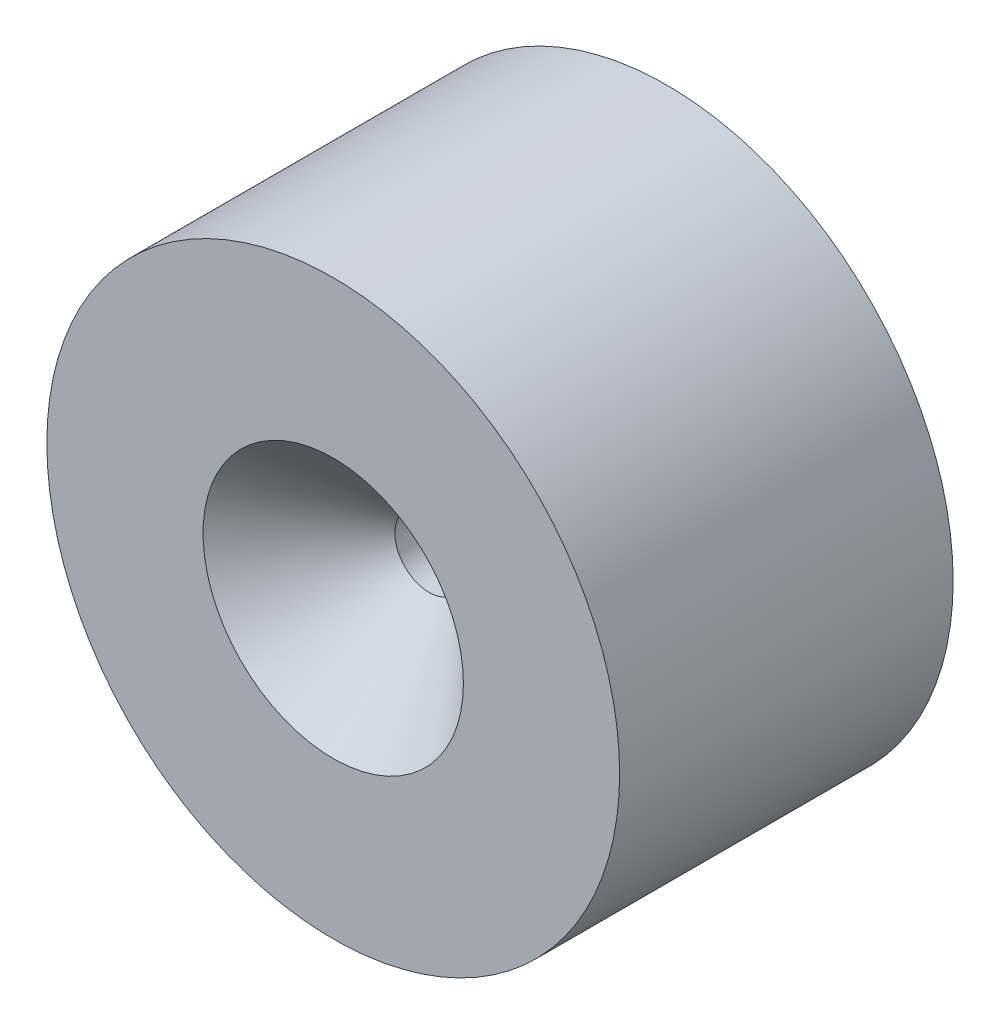
SolidWorks part; units mm, degrees
ref_plane "Front Plane" through (0, 0, 0) normal (0, 0, 1) x (1, 0, 0)
ref_plane "Top Plane" through (0, 0, 0) normal (0, 1, 0) x (1, 0, 0)
ref_plane "Right Plane" through (0, 0, 0) normal (1, 0, 0) x (0, 0, -1)
sketch "Sketch1" plane through (0, 0, 0) normal (0, 0, 1) x (1, 0, 0)
  circle A0 centre (0, 0) radius 26.543
extrude "Boss-Extrude1" add sketch "Sketch1" along normal blind 30.9118
ref_axis "Axis1" through (0, 0, -1.5456) along (0, 0, 1)
sketch "Sketch2" plane through (0, 0, 0) normal (1, 0, 0) x (0, 0, -1)
  line L0 (-30.9118, 12.065) -> (-22.0218, 3.175)
  line L1 (-30.9118, 26.543) -> (-30.9118, -26.543) construction
  line L2 (-22.0218, 3.175) -> (-18.2118, 3.175)
  line L3 (-18.2118, 3.175) -> (0, 4.7752)
  line L4 (0, -26.543) -> (0, 26.543) construction
  line L5 (0, 4.7752) -> (0, 0)
  line L6 (0, 0) -> (-30.9118, 0)
  line L7 (-30.9118, 0) -> (-30.9118, 12.065)
  line L8 (1.5456, 0) -> (-32.4574, 0) construction
  dimension "D1" = 12.065
  dimension "D2" = 3.175
  dimension "D3" = 4.7752
  dimension "D4" = 8.89
  dimension "D5" = 3.81
revolve "Cut-Revolve1" cut sketch "Sketch2" angle 360 about L6
